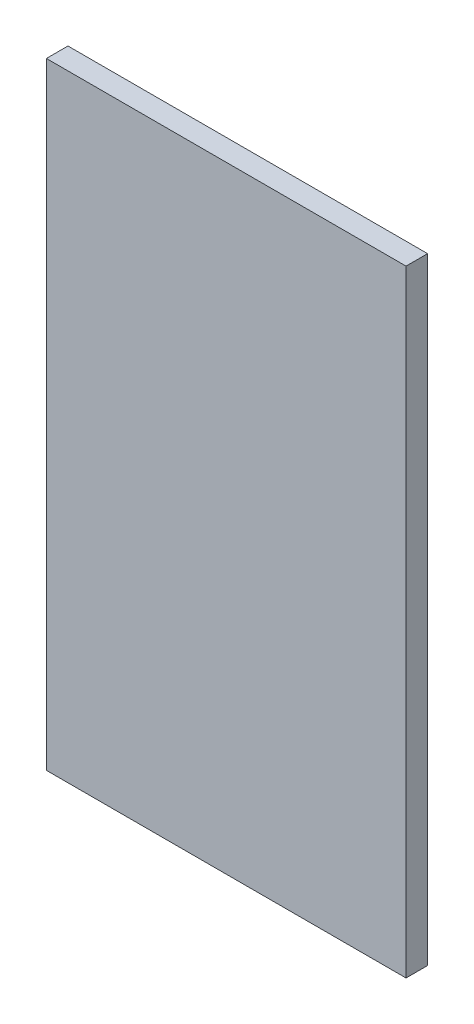
SolidWorks part; units mm, degrees
ref_plane "Front Plane" through (0, 0, 0) normal (0, 0, 1) x (1, 0, 0)
ref_plane "Top Plane" through (0, 0, 0) normal (0, 1, 0) x (1, 0, 0)
ref_plane "Right Plane" through (0, 0, 0) normal (1, 0, 0) x (0, 0, -1)
sketch "Sketch2" plane through (0, 0, 0) normal (0, 0, 1) x (1, 0, 0)
  line L1 (-44.45, -76.2) -> (44.45, -76.2)
  line L2 (-44.45, -76.2) -> (-44.45, 76.2)
  line L3 (-44.45, 76.2) -> (44.45, 76.2)
  line L4 (44.45, -76.2) -> (44.45, 76.2)
  line L5 (-44.45, -76.2) -> (44.45, 76.2) construction
  line L6 (-44.45, 76.2) -> (44.45, -76.2) construction
  point P0 (0, 0)
  dimension "D1" = 88.9
  dimension "D2" = 152.4
extrude "Boss-Extrude2" add sketch "Sketch2" along normal blind 5.334
equation "\"D1@Boss-Extrude2\" = \"material\""
equation "\"material\"=\"MDF@Platform.assembly\""
